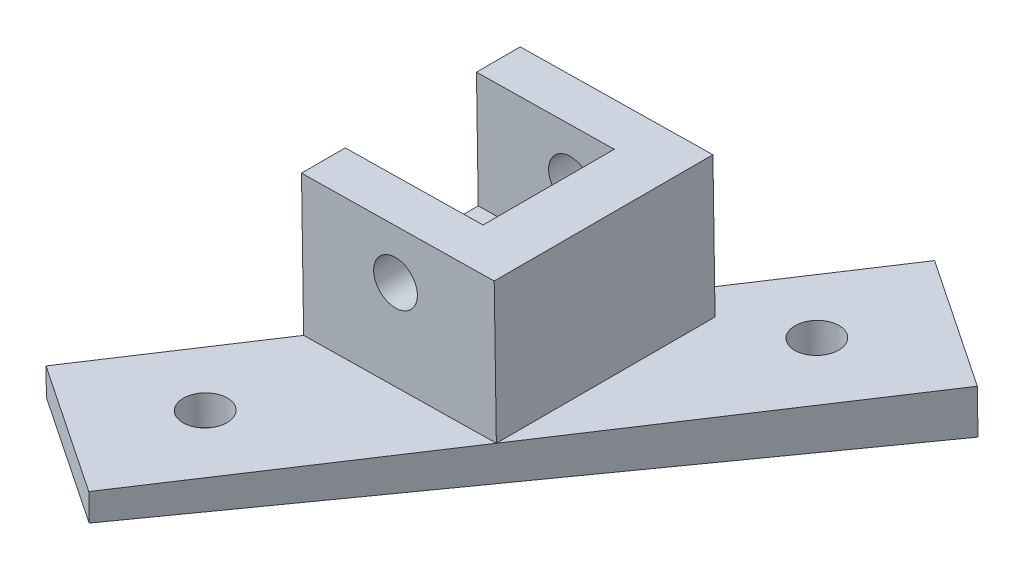
SolidWorks part; units mm, degrees
ref_plane "Front Plane" through (0, 0, 0) normal (0, 0, 1) x (1, 0, 0)
ref_plane "Top Plane" through (0, 0, 0) normal (0, 1, 0) x (1, 0, 0)
ref_plane "Right Plane" through (0, 0, 0) normal (1, 0, 0) x (0, 0, -1)
sketch "Sketch1" plane through (0, 0, 0) normal (0, 0, 1) x (1, 0, 0)
  line L0 (614.2482, 110.6197) -> (642.2246, 111.0468)
  line L1 (604.7125, 110.4741) -> (634.2525, 110.9251) construction
  line L2 (642.2246, 111.0468) -> (642.5336, 90.8054)
  line L3 (642.5336, 90.8054) -> (614.5573, 90.3783)
  line L4 (614.5573, 90.3783) -> (614.2482, 110.6197)
  line L5 (606.4491, 93.8109) -> (629.5989, 94.1643) construction
  line L6 (522.1487, 25.7254) -> (633.9027, 25.7254) construction
  line L7 (522.1487, 25.7254) -> (633.9027, 25.7254)
  line L8 (614.5573, 87.1817) -> (642.5336, 87.1817)
  line L9 (642.5336, 87.1817) -> (642.5336, 90.8054)
  line L10 (614.5573, 87.1817) -> (614.5573, 90.3783)
  line L15 (634.4712, 96.6012) -> (604.3912, 96.1419)
  line L16 (606.4491, 93.8109) -> (629.5989, 94.1643)
  line L18 (634.4712, 96.6012) -> (604.3912, 96.1419)
  line L19 (606.4491, 93.8109) -> (629.5989, 94.1643)
  arc A0 (634.4712, 96.6012) -> (634.2525, 110.9251) centre (627.8931, 103.6644) ccw construction
  arc A1 (634.2525, 110.9251) -> (634.4712, 96.6012) centre (627.8931, 103.6644) cw
  arc A3 (629.5989, 94.1643) -> (634.4712, 96.6012) centre (627.8931, 103.6644) ccw
  arc A4 (629.5989, 94.1643) -> (634.4712, 96.6012) centre (627.8931, 103.6644) ccw
  spline S2 degree 3 poles (4509.1692, 961.1582) (818.1256, 183.9997) (600.2483, 113.2338) (604.4885, 95.4418) (604.5493, 95.2808) (604.6964, 94.9846) (604.783, 94.8489) (604.9677, 94.606) (605.0672, 94.4967) (605.3783, 94.2032) (605.5939, 94.059) (622.0979, 86.4979) (616.4965, 349.142) (-1530.0994, 3471.6087) knots -12.746335 -12.746335 -12.746335 -12.746335 0.125 0.125 0.25 0.25 0.375 0.375 0.5 0.5 0.75 0.75 19.426718 19.426718 19.426718 19.426718 only from (604.3912, 96.1419) to (606.4491, 93.8109)
  spline S4 degree 3 poles (604.3912, 96.1419) (604.3871, 95.9602) (604.4069, 95.7841) (604.4885, 95.4418) (604.5493, 95.2808) (604.6964, 94.9846) (604.783, 94.8489) (604.9677, 94.606) (605.0672, 94.4967) (605.3783, 94.2032) (605.5939, 94.059) (606.0299, 93.8592) (606.244, 93.8078) (606.4491, 93.8109) knots 0 0 0 0 0.125 0.125 0.25 0.25 0.375 0.375 0.5 0.5 0.75 0.75 1 1 1 1
  dimension "D2" = 14.4425
  dimension "D1" = 3.556
  dimension "D3" = 0
extrude "Boss-Extrude2" add sketch "Sketch1" against normal up to surface (19.05 mm away) contours L19 L4 L3 L2 L0 A1 A4 region at (638.2439, 110.6378, 0)
sketch "Sketch2" plane through (0, 0, 0) normal (0, 0, 1) x (1, 0, 0)
  line L0 (614.5573, 90.3783) -> (614.2482, 110.6197)
  line L1 (604.7125, 110.4741) -> (634.2525, 110.9251) construction
  line L2 (614.2482, 110.6197) -> (642.2246, 111.0468)
  line L3 (642.2246, 111.0468) -> (642.5336, 90.8054)
  line L4 (642.5336, 90.8054) -> (614.5573, 90.3783)
extrude "Boss-Extrude3" add sketch "Sketch2" along normal blind 6.35 contours L4 L0 L2 L3
sketch "Sketch4" plane through (0, 0, -19.05) normal (0, 0, -1) x (-1, 0, 0)
  line L0 (-614.5573, 90.3783) -> (-614.2482, 110.6197)
  line L1 (-604.6203, 110.4727) -> (-634.2525, 110.9251) construction
  line L2 (-614.2482, 110.6197) -> (-642.2246, 111.0468)
  line L3 (-642.2246, 111.0468) -> (-642.5336, 90.8054)
  line L4 (-642.5336, 90.8054) -> (-614.5573, 90.3783)
extrude "Boss-Extrude4" add sketch "Sketch4" along normal blind 6.35
sketch "Sketch5" plane through (0, 0, 0) normal (0, 0, -1) x (-1, 0, 0)
  circle A0 centre (-627.8931, 103.6644) radius 3.175
extrude "Cut-Extrude1" cut sketch "Sketch5" against normal through all
sketch "Sketch6" plane through (0, 0, -19.05) normal (0, 0, 1) x (1, 0, 0)
  circle A0 centre (627.8931, 103.6644) radius 3.175
extrude "Cut-Extrude2" cut sketch "Sketch6" against normal through all
sketch "Sketch9" plane through (0, 0, 6.35) normal (0, 0, 1) x (1, 0, 0)
  line L2 (522.1487, 25.7254) -> (633.9027, 25.7254) construction
  line L3 (522.1487, 25.7254) -> (633.9027, 25.7254)
  line L6 (614.5573, 90.3783) -> (642.5336, 90.8054)
  line L7 (614.5573, 80.0701) -> (642.5898, 80.0701)
  line L8 (642.5898, 80.0701) -> (642.5336, 90.8054)
  line L9 (614.5573, 80.0701) -> (614.5573, 90.3783)
sketch "Sketch11" plane through (-1.2363, 80.9766, 0) normal (0.0153, -0.9999, 0) x (0.9999, 0.0153, 0)
  line L0 (615.8653, 6.35) -> (600.7721, 28.6587)
  line L1 (600.7721, 28.6587) -> (619.966, 41.6445)
  line L2 (619.966, 41.6445) -> (643.845, 6.35)
  line L3 (643.845, -25.4) -> (643.845, 6.35) construction
  line L4 (643.845, 6.35) -> (615.8653, 6.35) construction
  line L5 (643.845, 6.35) -> (672.0232, -35.299)
  line L6 (672.0232, -35.299) -> (652.8293, -48.2849)
  line L7 (652.8293, -48.2849) -> (615.8653, 6.35)
  dimension "D1" = 124.081
  dimension "D2" = 90
extrude "Boss-Extrude7" add sketch "Sketch11" along normal blind 7.874
sketch "Sketch12" plane through (-1.2363, 80.9766, 0) normal (-0.0153, 0.9999, 0) x (0.9999, 0.0153, 0)
  line L0 (643.845, -6.35) -> (619.966, -41.6445) construction
  line L1 (672.0232, 35.299) -> (643.845, -6.35) construction
  line L2 (619.966, -41.6445) -> (600.7721, -28.6587) construction
  line L3 (652.8293, 48.2849) -> (672.0232, 35.299) construction
  circle A0 centre (618.1913, -22.9636) radius 3.175
  circle A1 centre (654.0226, 29.9972) radius 3.175
  dimension "D1" = 11.938
  dimension "D2" = 11.938
  dimension "D3" = 14.478
  dimension "D4" = 14.478
extrude "Cut-Extrude4" cut sketch "Sketch12" against normal through all
sketch "Sketch13" plane through (444.5691, 6.7875, 300.8145) normal (0.8282, 0.0126, 0.5604) x (0.5603, 0.0086, -0.8282)
  line L0 (312.9136, 73.112) -> (312.9136, 73.0669)
  line L1 (312.9136, 73.0669) -> (405.7053, 70.6587)
  line L2 (405.7053, 70.6587) -> (405.8128, 73.112)
  line L3 (405.8128, 73.112) -> (312.9136, 73.112)
  line L5 (138.8906, 16.5856) -> (339.6635, 11.3751) construction
  line L6 (138.8906, 16.5856) -> (339.6635, 11.3751)
  line M9 (312.9136, 73.112) -> (405.8128, 73.112)
extrude "Boss-Extrude8" add sketch "Sketch13" against normal blind 23.1648 contours L1 L2 L0 M9 region at (653.1576, 82.2745, -9.1585)
sketch "Sketch14" plane through (444.5691, 6.7875, 300.8145) normal (0.8282, 0.0126, 0.5604) x (0.5603, 0.0086, -0.8282)
  line L0 (312.9136, 73.0669) -> (312.9136, 77.0455)
  line L1 (312.9136, 73.0669) -> (312.9136, 80.986) construction
  line L2 (312.9136, 77.0455) -> (405.8128, 74.6374)
  line L3 (405.8128, 73.112) -> (405.8128, 80.986) construction
  line L4 (405.8128, 74.6374) -> (405.7053, 70.6587)
  line L5 (405.7053, 70.6587) -> (312.9136, 73.0669)
  dimension "D1" = 3.9787
  dimension "D2" = 3.9787
extrude "Cut-Extrude6" cut sketch "Sketch14" against normal through all
